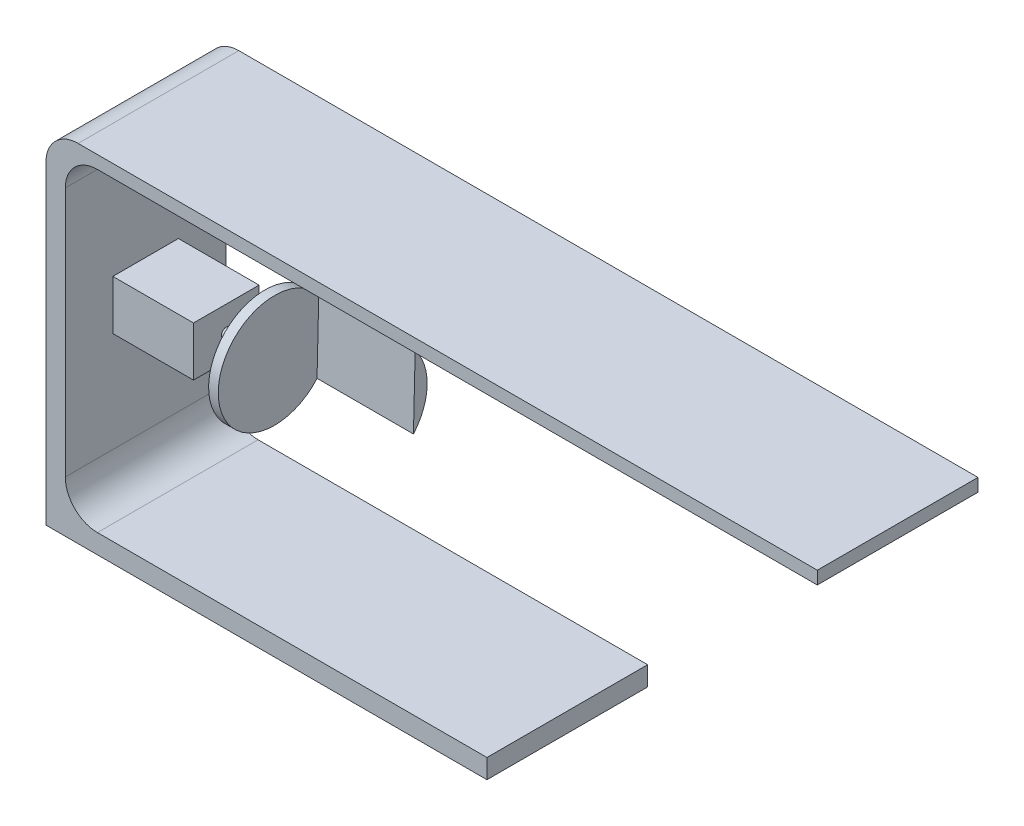
SolidWorks part; units mm, degrees
ref_plane "Front Plane" through (0, 0, 0) normal (0, 0, 1) x (1, 0, 0)
ref_plane "Top Plane" through (0, 0, 0) normal (0, 1, 0) x (1, 0, 0)
ref_plane "Right Plane" through (0, 0, 0) normal (1, 0, 0) x (0, 0, -1)
sketch "Sketch1" plane through (0, 0, 0) normal (0, 0, 1) x (1, 0, 0)
  line L0 (-102.7948, 0) -> (102.7948, 0)
  line L1 (102.7948, 0) -> (102.7948, -4)
  line L2 (102.7948, -4) -> (-121.2052, -4)
  line L3 (-131.2052, -14) -> (-131.2052, -91.8678)
  line L4 (-121.2052, -101.8678) -> (0, -101.8678)
  line L5 (0, -101.8678) -> (0, -107.8678)
  line L6 (0, -107.8678) -> (-137.2052, -107.8678)
  line L7 (-137.2052, -107.8678) -> (-137.2052, -10)
  line L8 (-127.2052, 0) -> (-102.7948, 0)
  arc A0 (-131.2052, -14) -> (-121.2052, -4) centre (-121.2052, -14) cw
  arc A1 (-131.2052, -91.8678) -> (-121.2052, -101.8678) centre (-121.2052, -91.8678) ccw
  arc A2 (-127.2052, 0) -> (-137.2052, -10) centre (-127.2052, -10) ccw
  point P4 (0, 0)
  point P18 (-137.2052, 0)
  dimension "D5" = 10
  dimension "D6" = 10
  dimension "D7" = 10
  dimension "D1" = 240
  dimension "D2" = 6
  dimension "D3" = 4
  dimension "D4" = 6
extrude "Boss-Extrude1" add sketch "Sketch1" along normal blind 25 and the other way blind 25
sketch "Sketch2" plane through (-131.2052, 0, 0) normal (1, 0, 0) x (0, 0, -1)
  line L0 (25, -14) -> (-25, -14) construction
  line L1 (-10.2, -60.6339) -> (10.2, -60.6339)
  line L2 (-10.2, -60.6339) -> (-10.2, -45.2339)
  line L3 (-10.2, -45.2339) -> (10.2, -45.2339)
  line L4 (10.2, -60.6339) -> (10.2, -45.2339)
  line L5 (-10.2, -60.6339) -> (10.2, -45.2339) construction
  line L6 (-10.2, -45.2339) -> (10.2, -60.6339) construction
  line L7 (0, -14) -> (0, -91.8678) construction
  line L8 (25, -91.8678) -> (-25, -91.8678) construction
  point P0 (0, -52.9339)
  point P11 (0, 0)
  point P12 (0, -52.9339)
  dimension "D1" = 20.4
  dimension "D2" = 15.4
extrude "Boss-Extrude2" add sketch "Sketch2" along normal blind 25.1 separate body
sketch "Sketch3" plane through (-106.1052, 0, 0) normal (1, 0, 0) x (0, 0, -1)
  line L0 (-10.2, -45.2339) -> (10.2, -60.6339) construction
  line L4 (10.2, -60.6339) -> (10.2, -45.2339)
  line L5 (10.2, -45.2339) -> (-10.2, -45.2339)
  line L6 (-10.2, -45.2339) -> (-10.2, -60.6339)
  line L7 (-10.2, -60.6339) -> (10.2, -60.6339)
  line L8 (10.2, -60.6339) -> (10.2, -45.2339) construction
  line L9 (10.2, -45.2339) -> (-10.2, -45.2339) construction
  line L10 (-10.2, -45.2339) -> (-10.2, -60.6339) construction
  line L11 (-10.2, -60.6339) -> (10.2, -60.6339) construction
  circle A0 centre (0, -52.9339) radius 1.5
  dimension "D2" = 3
  dimension "D1" = 0
extrude "Boss-Extrude3" add sketch "Sketch3" along normal blind 12 separate body
sketch "Sketch4" plane through (-94.1052, 0, 0) normal (1, 0, 0) x (0, 0, -1)
  circle A0 centre (0, -52.9339) radius 17.5
  circle A1 centre (0, -52.9339) radius 1.5
  circle A2 centre (0, -52.9339) radius 1.5 construction
  dimension "D2" = 35
  dimension "D1" = 0
extrude "Boss-Extrude4" add sketch "Sketch4" along normal blind 3
sketch "Sketch5" plane through (-91.1052, 0, 0) normal (1, 0, 0) x (0, 0, -1)
  line L0 (13.7692, -42.1329) -> (13.2371, -64.3807)
  circle A1 centre (0, -52.9339) radius 17.5
  arc A2 (13.2371, -64.3807) -> (13.7692, -42.1329) centre (0, -52.9339) ccw
  dimension "D1" = 0
extrude "Boss-Extrude5" add sketch "Sketch5" along normal blind 30
